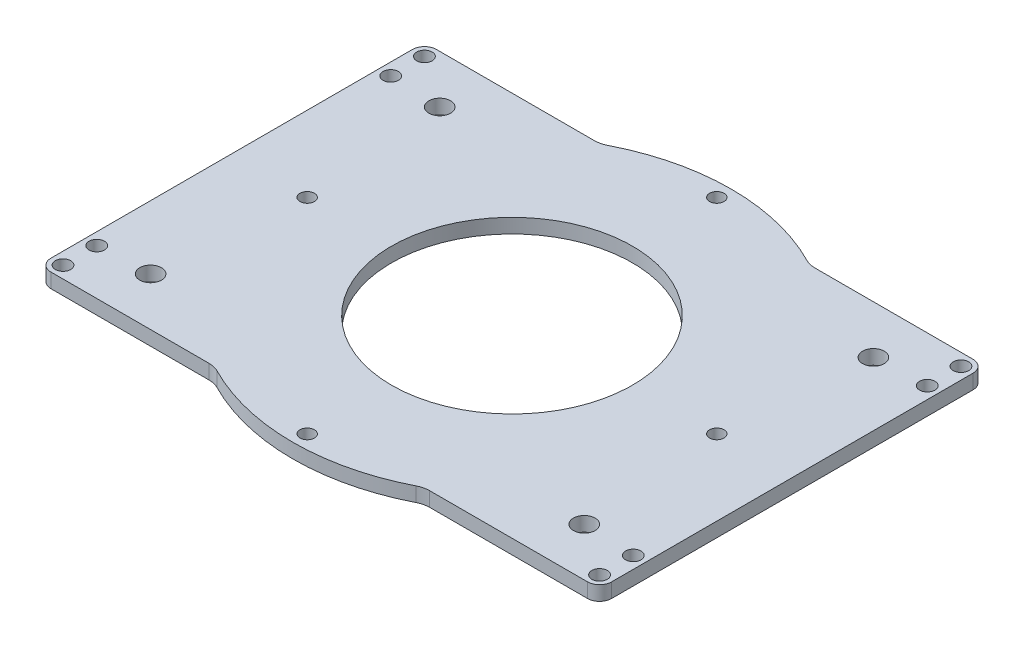
SolidWorks part; units mm, degrees
ref_plane "Front Plane" through (0, 0, 0) normal (0, 0, 1) x (1, 0, 0)
ref_plane "Top Plane" through (0, 0, 0) normal (0, 1, 0) x (1, 0, 0)
ref_plane "Right Plane" through (0, 0, 0) normal (1, 0, 0) x (0, 0, -1)
sketch "Sketch1" plane through (0, 0, 0) normal (0, 1, 0) x (1, 0, 0)
  line L0 (0, 0) -> (0, 42.5) construction
  line L1 (45, -30) -> (-45, -30) construction
  line L2 (45, -30) -> (45, 30) construction
  line L3 (45, 30) -> (-45, 30) construction
  line L4 (-45, -30) -> (-45, 30) construction
  line L5 (45, -30) -> (-45, 30) construction
  line L6 (45, 30) -> (-45, -30) construction
  line L7 (55.675, -40) -> (-55.675, -40) construction
  line L8 (58.175, -37.5) -> (58.175, 37.5)
  line L9 (55.675, 40) -> (-55.675, 40) construction
  line L10 (-58.175, -37.5) -> (-58.175, 37.5)
  line L11 (58.175, -40) -> (-58.175, 40) construction
  line L12 (58.175, 40) -> (-58.175, -40) construction
  line L13 (0, 0) -> (42.5, 0) construction
  line L14 (-55.675, 40) -> (-22.9183, 40)
  line L15 (22.9183, 40) -> (55.675, 40)
  line L16 (22.9183, -40) -> (55.675, -40)
  line L17 (-55.675, -40) -> (-22.9183, -40)
  line L18 (55.675, 37.5) -> (55.675, 30.5) construction
  line L20 (55.675, 37.5) -> (55.675, 40) construction
  circle A0 centre (-45, 30) radius 2.25
  circle A1 centre (-45, -30) radius 2.25
  circle A2 centre (45, -30) radius 2.25
  circle A3 centre (45, 30) radius 2.25
  circle A4 centre (0, 0) radius 25
  arc A5 (-58.175, -37.5) -> (-55.675, -40) centre (-55.675, -37.5) ccw
  arc A6 (55.675, -40) -> (58.175, -37.5) centre (55.675, -37.5) ccw
  arc A7 (58.175, 37.5) -> (55.675, 40) centre (55.675, 37.5) ccw
  arc A8 (-55.675, 40) -> (-58.175, 37.5) centre (-55.675, 37.5) ccw
  circle A9 centre (0, 0) radius 42.5 construction
  circle A10 centre (0, 42.5) radius 1.5
  circle A11 centre (42.5, 0) radius 1.5
  circle A12 centre (0, -42.5) radius 1.5
  circle A13 centre (-42.5, 0) radius 1.5
  arc A14 (20.6492, 40.5446) -> (-20.6492, 40.5446) centre (0, 0) ccw
  arc A15 (22.9183, 40) -> (20.6492, 40.5446) centre (22.9183, 45) cw
  arc A16 (-20.6492, 40.5446) -> (-22.9183, 40) centre (-22.9183, 45) cw
  arc A17 (22.9183, -40) -> (20.6492, -40.5446) centre (22.9183, -45) ccw
  arc A18 (20.6492, -40.5446) -> (-20.6492, -40.5446) centre (0, 0) cw
  arc A19 (-20.6492, -40.5446) -> (-22.9183, -40) centre (-22.9183, -45) ccw
  circle A20 centre (55.675, 37.5) radius 1.6
  circle A21 centre (55.675, 30.5) radius 1.6
  circle A22 centre (-55.675, 30.5) radius 1.6
  circle A23 centre (-55.675, 37.5) radius 1.6
  circle A24 centre (-55.675, -37.5) radius 1.6
  circle A25 centre (-55.675, -30.5) radius 1.6
  circle A26 centre (55.675, -37.5) radius 1.6
  circle A27 centre (55.675, -30.5) radius 1.6
  point P0 (0, 0)
  point P41 (21.6852, 40)
  point P44 (-21.6852, 40)
  dimension "D1" = 4.5
  dimension "D4" = 50
  dimension "D7" = 2
  dimension "D8" = 85
  dimension "D9" = 3
  dimension "D10" = 3
  dimension "D11" = 5
  dimension "D5" = 40
  dimension "D12" = 3.2
  dimension "D2" = 90
  dimension "D3" = 60
  dimension "D6" = 116.35
  dimension "D13" = 7
  dimension "D14" = 2.5
  dimension "D15" = 2.5
  dimension "D16" = 2
extrude "Boss-Extrude1" add sketch "Sketch1" along normal blind 3
